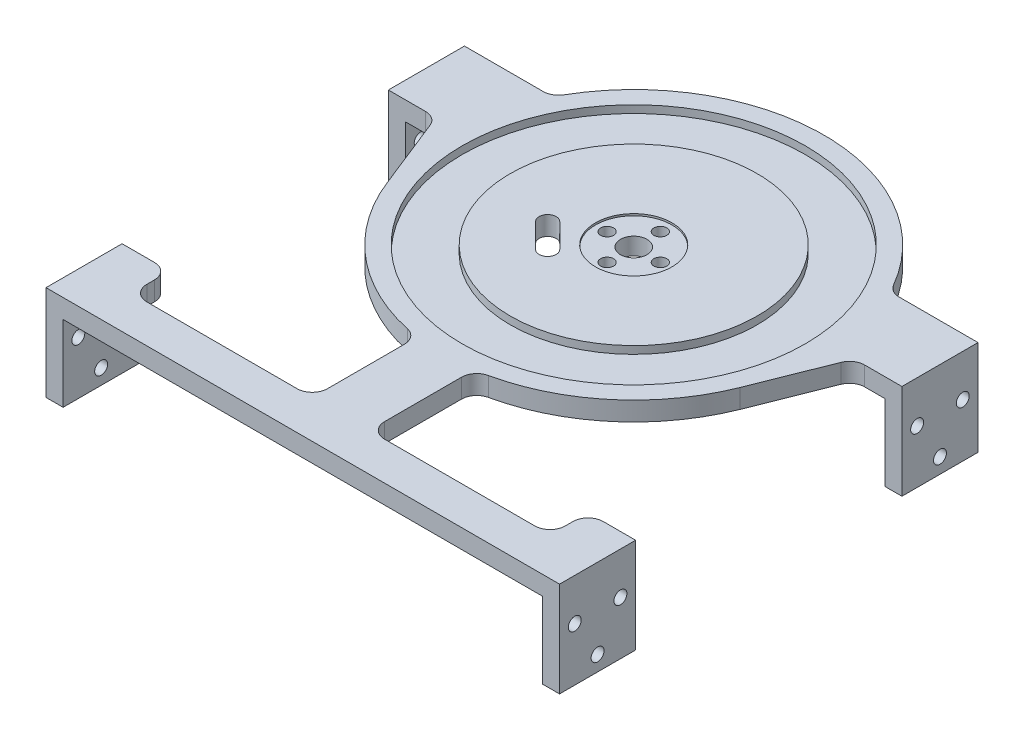
SolidWorks part; units mm, degrees
ref_plane "前视基准面" through (0, 0, 0) normal (0, 0, 1) x (1, 0, 0)
ref_plane "上视基准面" through (0, 0, 0) normal (0, 1, 0) x (1, 0, 0)
ref_plane "右视基准面" through (0, 0, 0) normal (1, 0, 0) x (0, 0, -1)
sketch "草图1" plane through (0, 0, 0) normal (0, 1, 0) x (1, 0, 0)
  line L0 (0, 32) -> (0, 0) construction
  line L1 (-63, 55) -> (63, 55) construction
  line L2 (-63, 55) -> (-63, -55) construction
  line L3 (-63, -55) -> (63, -55) construction
  line L4 (63, 55) -> (63, -55) construction
  line L5 (-63, 55) -> (63, -55) construction
  line L6 (-63, -55) -> (63, 55) construction
  line L7 (-63, 55) -> (-55, 55)
  line L8 (-63, 55) -> (-63, 35)
  line L9 (-63, 35) -> (-55, 35)
  line L10 (-55, 55) -> (-55, 35)
  line L11 (-63, -55) -> (-55, -55)
  line L12 (-63, -55) -> (-63, -35)
  line L13 (-63, -35) -> (-55, -35)
  line L14 (-55, -55) -> (-55, -35)
  line L15 (63, 55) -> (55, 55)
  line L16 (63, 55) -> (63, 35)
  line L17 (63, 35) -> (55, 35)
  line L18 (55, 55) -> (55, 35)
  line L19 (63, -55) -> (55, -55)
  line L20 (63, -55) -> (63, -35)
  line L21 (63, -35) -> (55, -35)
  line L22 (55, -55) -> (55, -35)
  line L23 (-55, 55) -> (-44.3959, 55)
  line L24 (-55, 35) -> (-46.4622, 13.5266)
  line L25 (55, 55) -> (44.3959, 55)
  line L26 (55, 35) -> (46.4622, 13.5266)
  line L27 (-55, -45) -> (55, -45)
  line L28 (55, -55) -> (-55, -55)
  line L29 (0, -45) -> (0, -18) construction
  line L30 (-7.5, -45) -> (-7.5, -17.4343)
  line L31 (7.5, -45) -> (7.5, -17.4343)
  line L32 (-59, 55) -> (-59, 35) construction
  line L33 (59, 55) -> (59, 35) construction
  line L34 (59, -35) -> (59, -55) construction
  line L35 (-59, -35) -> (-59, -55) construction
  line L36 (-55, -55) -> (55, -55)
  circle A0 centre (0, 32) radius 50
  point P0 (0, 0)
  dimension "D6" = 100
  dimension "D1" = 126
  dimension "D2" = 110
  dimension "D3" = 8
  dimension "D4" = 20
  dimension "D5" = 32
  dimension "D17" = 15
extrude "凸台-拉伸1" add sketch "草图1" along normal blind 5 contours L28 L22 L27 L14 | L11 L14 L13 L12 | A0 L30 L27 L31 | L22 L19 L20 L21 | L15 L18 L17 L16 | A0 L26 L18 L25 | A0 | L10 L7 L8 L9 | A0 L23 L10 L24 region at (-59, 0, -45) region at (-51.2758, 0, -42.8025) region at (0, 0, -32) region at (51.2758, 0, -42.8025) region at (0, 0, 31.4054) region at (59, 0, -45) region at (0, 0, 50) region at (-59, 0, 45) region at (59, 0, 45)
sketch "草图2" plane through (63, 0, 0) normal (1, 0, 0) x (0, 0, -1)
  line L0 (45, -16) -> (45, 0) construction
  line L1 (35, 0) -> (55, 0)
  line L2 (35, 0) -> (35, -20)
  line L3 (35, -20) -> (55, -20)
  line L4 (35, 0) -> (55, 0)
  line L5 (55, 0) -> (55, 5)
  line L6 (55, 5) -> (35, 5)
  line L7 (35, 5) -> (35, 0)
  line L8 (35, 0) -> (55, 0)
  line L9 (55, 0) -> (55, 5)
  line L10 (55, 5) -> (35, 5)
  line L11 (35, 5) -> (35, 0)
  line L12 (55, 0) -> (55, -20)
  line L13 (39, -6) -> (51, -6) construction
  circle A0 centre (39, -6) radius 1.7
  circle A1 centre (51, -6) radius 1.7
  circle A2 centre (45, -16) radius 1.7
  point P20 (45, -6)
  line M14 (35, 0) -> (55, 0)
  line M15 (55, 0) -> (55, 5)
  line M16 (55, 5) -> (35, 5)
  line M17 (35, 5) -> (35, 0)
  dimension "D3" = 3.4
  dimension "D2" = 20
  dimension "D4" = 16
  dimension "D5" = 12
  dimension "D6" = 6
  dimension "D1" = 0
extrude "凸台-拉伸2" add sketch "草图2" along normal blind 4.5 contours L12 L2 L3 A2 A1 A0 M14 | M17 M14 M15 M16 region at (63, 2.5, -45) region at (63, -10.0487, -45)
mirror "镜向1" about plane through (0, 0, 0) normal (0, 0, 1) of "凸台-拉伸2"
mirror "镜向2" about plane through (0, 0, 0) normal (1, 0, 0) of "凸台-拉伸2", "镜向1"
sketch "草图3" plane through (0, 5, 0) normal (0, 1, 0) x (1, 0, 0)
  circle A0 centre (0, 32) radius 50
  circle A1 centre (0, 32) radius 45.1
  circle A2 centre (0, 32) radius 32.45
  circle A3 centre (0, 32) radius 10.05
  circle A4 centre (0, 32) radius 7 construction
  circle A5 centre (0, 39) radius 1.7
  circle A6 centre (7, 32) radius 1.7
  circle A7 centre (0, 25) radius 1.7
  circle A8 centre (-7, 32) radius 1.7
  circle A9 centre (0, 32) radius 3.5
  dimension "D1" = 90.2
  dimension "D2" = 64.9
  dimension "D3" = 20.1
  dimension "D4" = 14
  dimension "D5" = 3.4
  dimension "D6" = 7
extrude "切除-拉伸1" cut sketch "草图3" against normal blind 2 contours A1 A2 region at (-43.8244, 5, -32)
extrude "切除-拉伸2" cut sketch "草图3<3>" against normal through all contours A5 | A6 | A7 | A8 | A9 region at (0, 5, -39) region at (7, 5, -32) region at (0, 5, -25) region at (-7, 5, -32)
sketch "草图3<3>" plane through (0, 5, 0) normal (0, 1, 0) x (1, 0, 0) same geometry as "草图3"
extrude "切除-拉伸3" cut sketch "草图3<4>" against normal blind 0.5 contours A3 A8 A7 A6 A5 region at (-9.7657, 5, -32)
sketch "草图3<4>" plane through (0, 5, 0) normal (0, 1, 0) x (1, 0, 0) same geometry as "草图3"
sketch "草图4" plane through (0, 5, 0) normal (0, 1, 0) x (1, 0, 0)
  line L0 (-16.617, 25.9896) -> (-10.253, 19.6256) construction
  line L1 (-15.026, 27.5806) -> (-8.6621, 21.2166)
  line L2 (-18.208, 24.3986) -> (-11.844, 18.0346)
  line L3 (-11.3137, 20.6863) -> (0, 32) construction
  line L4 (0, 32) -> (-7.3256, 32)
  arc A0 (-15.026, 27.5806) -> (-18.208, 24.3986) centre (-16.617, 25.9896) ccw
  arc A1 (-11.844, 18.0346) -> (-8.6621, 21.2166) centre (-10.253, 19.6256) ccw
  circle A2 centre (0, 32) radius 3.5 construction
  circle A3 centre (0, 32) radius 3.5
  point P2 (-13.435, 22.8076)
  dimension "D1" = 9
  dimension "D2" = 4.5
  dimension "D3" = 16
  dimension "D4" = 3
  dimension "D5" = 45
extrude "切除-拉伸4" cut sketch "草图4" against normal through all contours L2 A1 L1 A0 region at (-13.435, 5, -22.8076)
fillet "圆角1" radius 4 12 edges at (55, 2.5, -35) (55, 2.5, 35) (55, 2.5, 45) (7.5, 2.5, 17.4343) (7.5, 2.5, 45) (-55, 2.5, 35) (-55, 2.5, 45) (-7.5, 2.5, 45) (-7.5, 2.5, 17.4343) (-55, 2.5, -35) (-44.3959, 2.5, -55) (44.3959, 2.5, -55)
